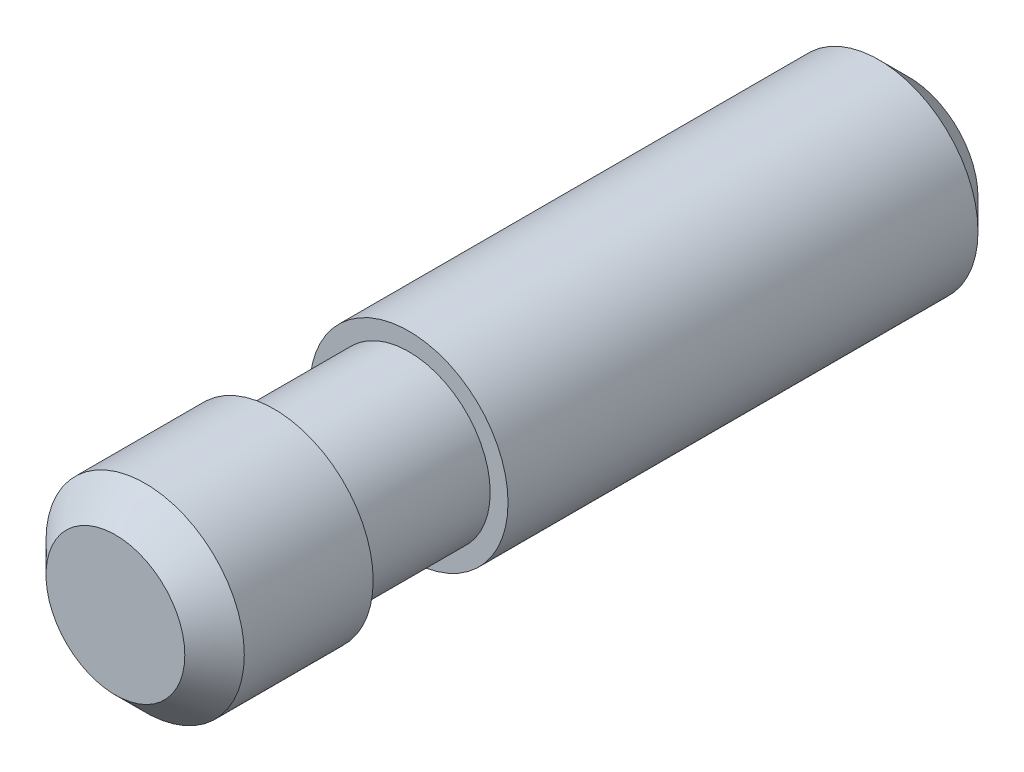
SolidWorks part; units mm, degrees
material "5086-H32, Стержень (SS)"
ref_plane "Спереди" through (0, 0, 0) normal (0, 0, 1) x (1, 0, 0)
ref_plane "Сверху" through (0, 0, 0) normal (0, 1, 0) x (1, 0, 0)
ref_plane "Справа" through (0, 0, 0) normal (1, 0, 0) x (0, 0, -1)
sketch "Эскиз1" plane through (0, 0, 0) normal (0, 0, 1) x (1, 0, 0)
  circle A0 centre (0, 0) radius 2.5
  dimension "D1" = 5
extrude "Бобышка-Вытянуть1" add sketch "Эскиз1" along normal blind 20
chamfer "Фаска1" distance 0.75 2 edges at (2.5, 0, 20) (2.5, 0, 0)
sketch "Эскиз2" plane through (0, 0, 0) normal (1, 0, 0) x (0, 0, -1)
  line L0 (-16, 2.5) -> (-16, 2.05)
  line L1 (-0.75, 2.5) -> (-19.25, 2.5) construction
  line L2 (-16, 2.05) -> (-12.6, 2.05)
  line L3 (-12.6, 2.05) -> (-12.6, 2.5)
  line L4 (-20, 1.75) -> (-20, -1.75) construction
  line L5 (-16, 2.5) -> (-12.6, 2.5)
  dimension "D1" = 0.45
  dimension "D2" = 4
  dimension "D3" = 3.4
ref_axis "Ось1" through (0, 0, 0) along (0, 0, 1)
sketch "Эскиз4" plane through (0, 0, 0) normal (1, 0, 0) x (0, 0, -1)
  line L0 (-20, 0) -> (0, 0)
  line L1 (-20, 1.75) -> (-20, -1.75) construction
revolve "Вырез-Повернуть1" cut sketch "Эскиз2" angle 360 about L0
